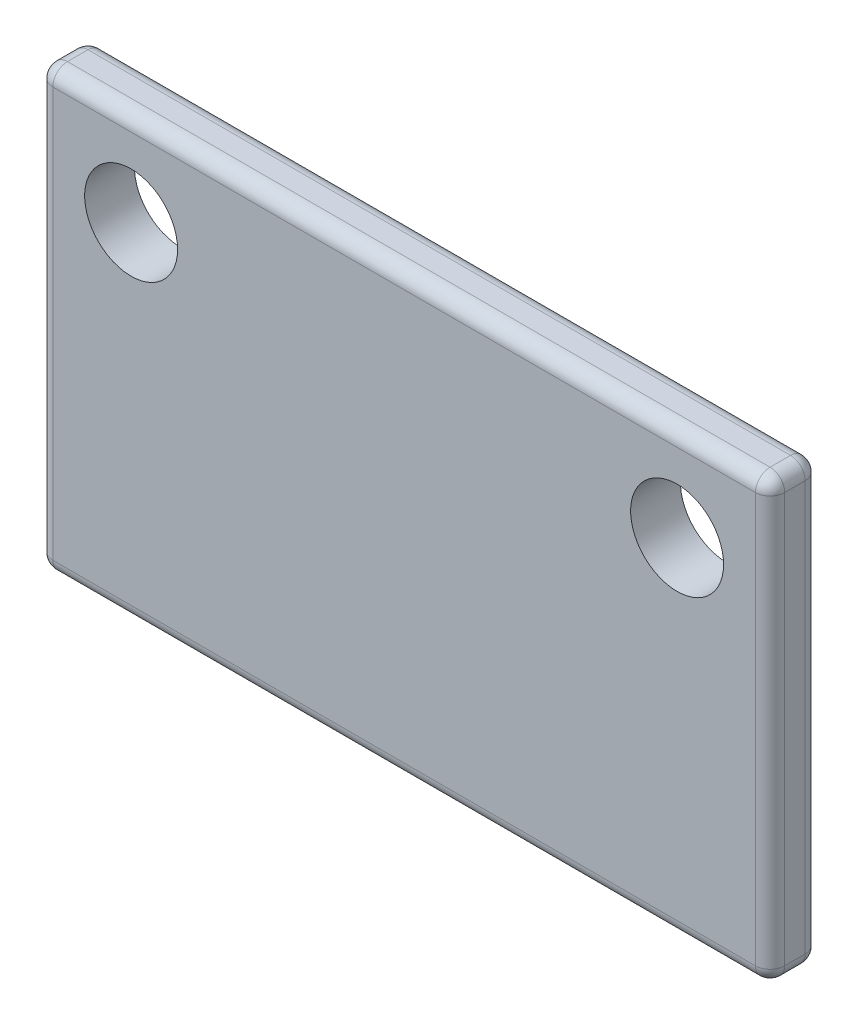
SolidWorks part; units mm, degrees
ref_plane "Plano frontal" through (0, 0, 0) normal (0, 0, 1) x (1, 0, 0)
ref_plane "Plano superior" through (0, 0, 0) normal (0, 1, 0) x (1, 0, 0)
ref_plane "Plano direito" through (0, 0, 0) normal (1, 0, 0) x (0, 0, -1)
sketch "Esboço1" plane through (0, 0, 0) normal (0, 0, 1) x (1, 0, 0)
  line L1 (12.5, -7.5) -> (-12.5, -7.5)
  line L2 (12.5, -7.5) -> (12.5, 7.5)
  line L3 (12.5, 7.5) -> (-12.5, 7.5)
  line L4 (-12.5, -7.5) -> (-12.5, 7.5)
  line L5 (12.5, -7.5) -> (-12.5, 7.5) construction
  line L6 (12.5, 7.5) -> (-12.5, -7.5) construction
  point P0 (0, 0)
  dimension "D1" = 25
  dimension "D2" = 15
extrude "Ressalto-extrusão1" add sketch "Esboço1" along normal blind 1.7
sketch "Esboço2" plane through (0, 0, 1.7) normal (0, 0, 1) x (1, 0, 0)
  line L1 (-12.5, 7.5) -> (-9.325, 7.5) construction
  line L2 (-12.5, 7.5) -> (-12.5, 4.325) construction
  line L3 (-12.5, 4.325) -> (-9.325, 4.325) construction
  line L4 (-12.5, 7.5) -> (-12.5, -7.5)
  line L5 (-12.5, -7.5) -> (12.5, -7.5)
  line L6 (12.5, -7.5) -> (12.5, 7.5)
  line L7 (12.5, 7.5) -> (-12.5, 7.5)
  line L8 (-12.5, 7.5) -> (-12.5, -7.5) construction
  line L9 (-12.5, -7.5) -> (12.5, -7.5)
  line L10 (12.5, -7.5) -> (12.5, 7.5) construction
  line L11 (12.5, 7.5) -> (-12.5, 7.5) construction
  line L12 (-9.325, 7.5) -> (-9.325, 4.325) construction
  line L13 (12.5, 7.5) -> (9.325, 7.5) construction
  line L14 (12.5, 7.5) -> (12.5, 4.325) construction
  line L15 (12.5, 4.325) -> (9.325, 4.325) construction
  line L16 (9.325, 7.5) -> (9.325, 4.325) construction
  circle A0 centre (-9.325, 4.325) radius 1.5875
  circle A1 centre (9.325, 4.325) radius 1.5875
  dimension "D3" = 3.175
  dimension "D2" = 3.175
  dimension "D1" = 0
extrude "Corte-extrusão1" cut sketch "Esboço2" against normal through all contours A0 | A1 region at (-9.325, 4.325, 1.7) region at (9.325, 4.325, 1.7)
fillet "Filete2" radius 0.5 12 edges at (0, -7.5, 0) (12.5, 0, 0) (-12.5, 0, 1.7) (0, -7.5, 1.7) (12.5, 0, 1.7) (0, 7.5, 1.7) (12.5, 7.5, 0.85) (12.5, -7.5, 0.85) (-12.5, -7.5, 0.85) (-12.5, 7.5, 0.85) (-12.5, 0, 0) (0, 7.5, 0)
